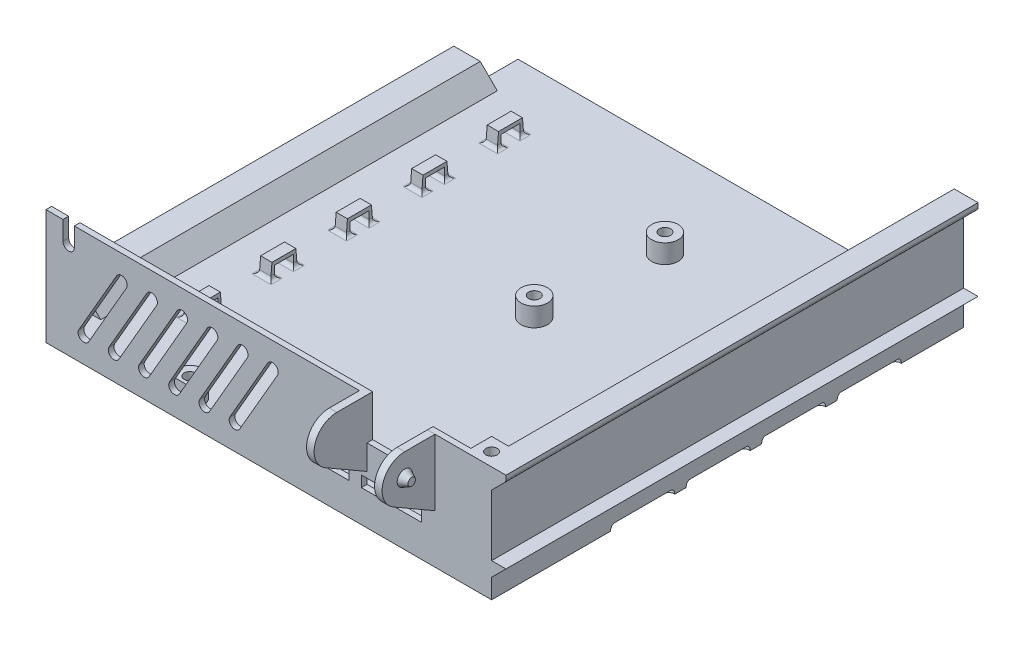
SolidWorks part; units mm, degrees
material "ABS"
ref_plane "Front Plane" through (0, 0, 0) normal (0, 0, 1) x (1, 0, 0)
ref_plane "Top Plane" through (0, 0, 0) normal (0, 1, 0) x (1, 0, 0)
ref_plane "Right Plane" through (0, 0, 0) normal (1, 0, 0) x (0, 0, -1)
ref_axis "Axis1" through (0, 0, 22) along (0, 0, -1)
sketch "Sketch1" plane through (0, 0, 0) normal (0, 1, 0) x (1, 0, 0)
  line L0 (-125, 0) -> (0, 0) construction
  line L1 (125, 0) -> (125, 125) construction
  line L2 (125, 125) -> (-125, 125) construction
  line L3 (-125, 125) -> (-125, 0) construction
  line L4 (41.25, 3.85) -> (41.25, 1.6) construction
  line L5 (39, 101.6) -> (109, 101.6)
  line L6 (39, 101.6) -> (39, 1.6)
  line L7 (39, 1.6) -> (109, 1.6)
  line L8 (109, 101.6) -> (109, 1.6)
  line L9 (39, 101.6) -> (109, 1.6) construction
  line L10 (39, 1.6) -> (109, 101.6) construction
  line L11 (41.25, 3.85) -> (39, 3.85) construction
  line L12 (-114.29, 77.51) -> (-116.54, 77.51) construction
  line L13 (78.2, 11.6) -> (87.2, 11.6)
  line L14 (78.2, 11.6) -> (78.2, 1.6)
  line L15 (78.2, 1.6) -> (87.2, 1.6)
  line L16 (87.2, 11.6) -> (87.2, 1.6)
  line L17 (78.2, 11.6) -> (87.2, 1.6) construction
  line L18 (78.2, 1.6) -> (87.2, 11.6) construction
  line L19 (90.5, 16.6) -> (106.5, 16.6)
  line L20 (90.5, 16.6) -> (90.5, 1.6)
  line L21 (90.5, 1.6) -> (106.5, 1.6)
  line L22 (106.5, 16.6) -> (106.5, 1.6)
  line L23 (90.5, 16.6) -> (106.5, 1.6) construction
  line L24 (90.5, 1.6) -> (106.5, 16.6) construction
  line L25 (-116.54, 113.59) -> (-93.46, 113.59)
  line L26 (-116.54, 113.59) -> (-116.54, 71.41)
  line L27 (-116.54, 71.41) -> (-93.46, 71.41)
  line L28 (-93.46, 113.59) -> (-93.46, 71.41)
  line L29 (-116.54, 113.59) -> (-93.46, 71.41) construction
  line L30 (-116.54, 71.41) -> (-93.46, 113.59) construction
  line L31 (-114.29, 77.51) -> (-114.29, 71.41) construction
  line L32 (-95.71, 107.49) -> (-95.71, 113.59) construction
  line L33 (-95.71, 107.49) -> (-93.46, 107.49) construction
  line L34 (-64.5, 85.45) -> (-68, 85.45) construction
  line L35 (-65, 88.95) -> (-15, 88.95)
  line L36 (-68, 85.95) -> (-68, 6.95)
  line L37 (-65, 3.95) -> (-15, 3.95)
  line L38 (-12, 85.95) -> (-12, 6.95)
  line L39 (-68, 88.95) -> (-12, 3.95) construction
  line L40 (-68, 3.95) -> (-12, 88.95) construction
  line L41 (-64.5, 85.45) -> (-15.5, 85.45) construction
  line L42 (-64.5, 85.45) -> (-64.5, 27.45) construction
  line L43 (-64.5, 27.45) -> (-15.5, 27.45) construction
  line L44 (-15.5, 85.45) -> (-15.5, 27.45) construction
  line L45 (0, 0) -> (0, 125) construction
  line L46 (0, 0) -> (125, 0) construction
  line L47 (-64.5, 85.45) -> (-64.5, 88.95) construction
  line L48 (74, 0.1) -> (74, 125) construction
  line L49 (-65.69, 22.9) -> (-49.81, 22.9)
  line L50 (-65.69, 22.9) -> (-65.69, 1.5)
  line L51 (-65.69, 1.5) -> (-49.81, 1.5)
  line L52 (-49.81, 22.9) -> (-49.81, 1.5)
  line L53 (-65.69, 22.9) -> (-49.81, 1.5) construction
  line L54 (-65.69, 1.5) -> (-49.81, 22.9) construction
  line L55 (-45.65, 19.42) -> (-32.35, 19.42)
  line L56 (-45.65, 19.42) -> (-45.65, 1.5)
  line L57 (-45.65, 1.5) -> (-32.35, 1.5)
  line L58 (-32.35, 19.42) -> (-32.35, 1.5)
  line L59 (-45.65, 19.42) -> (-32.35, 1.5) construction
  line L60 (-45.65, 1.5) -> (-32.35, 19.42) construction
  line L61 (-27.65, 19.42) -> (-14.35, 19.42)
  line L62 (-27.65, 19.42) -> (-27.65, 1.5)
  line L63 (-27.65, 1.5) -> (-14.35, 1.5)
  line L64 (-14.35, 19.42) -> (-14.35, 1.5)
  line L65 (-27.65, 19.42) -> (-14.35, 1.5) construction
  line L66 (-27.65, 1.5) -> (-14.35, 19.42) construction
  line L67 (-40, 0) -> (-40, 125) construction
  line L68 (-114.29, 11.41) -> (-114.29, 17.51) construction
  line L69 (-116.54, 53.59) -> (-93.46, 53.59)
  line L70 (-116.54, 53.59) -> (-116.54, 11.41)
  line L71 (-116.54, 11.41) -> (-93.46, 11.41)
  line L72 (-93.46, 53.59) -> (-93.46, 11.41)
  line L73 (-116.54, 53.59) -> (-93.46, 11.41) construction
  line L74 (-116.54, 11.41) -> (-93.46, 53.59) construction
  line L75 (-114.29, 17.51) -> (-116.54, 17.51) construction
  line L76 (-95.71, 53.59) -> (-95.71, 47.49) construction
  line L77 (-95.71, 47.49) -> (-93.46, 47.49) construction
  line L78 (-105, 0) -> (-105, 32.5) construction
  line L79 (-105, 32.5) -> (-105, 92.5) construction
  line L80 (-105, 92.5) -> (-105, 125) construction
  line L81 (-64.5, 27.45) -> (-15.5, 85.45) construction
  line L82 (-15.5, 27.45) -> (-64.5, 85.45) construction
  circle A0 centre (106, 81.6) radius 1.75
  circle A1 centre (106, 19.6) radius 1.75
  circle A2 centre (71.1, 99.8) radius 1.75
  circle A3 centre (68.3, 68) radius 1.75
  circle A4 centre (41.25, 3.85) radius 1.75
  circle A5 centre (-95.71, 107.49) radius 1.4
  circle A6 centre (-114.29, 77.51) radius 1.4
  arc A7 (-15, 3.95) -> (-12, 6.95) centre (-15, 6.95) ccw
  arc A8 (-68, 6.95) -> (-65, 3.95) centre (-65, 6.95) ccw
  arc A9 (-15, 88.95) -> (-12, 85.95) centre (-15, 85.95) cw
  arc A10 (-65, 88.95) -> (-68, 85.95) centre (-65, 85.95) ccw
  circle A11 centre (-64.5, 85.45) radius 1.375
  circle A12 centre (-15.5, 85.45) radius 1.375
  circle A13 centre (-64.5, 27.45) radius 1.375
  circle A14 centre (-15.5, 27.45) radius 1.375
  circle A15 centre (-95.71, 47.49) radius 1.4
  circle A16 centre (-114.29, 17.51) radius 1.4
  circle A17 centre (41.25, 3.85) radius 2.84
  point P0 (74, 51.6)
  point P3 (-105, 92.5)
  point P4 (0, 0)
  point P24 (82.7, 6.6)
  point P30 (98.5, 9.1)
  point P47 (-40, 46.45)
  point P65 (-39, 10.46)
  point P69 (-57.75, 12.2)
  point P84 (-21, 10.46)
  point P89 (-105, 32.5)
  point P111 (-40, 56.45)
  dimension "D5" = 3.5
  dimension "D26" = 3
  dimension "D27" = 2.75
  dimension "D44" = 2.8
  dimension "D49" = 5.68
  dimension "D1" = 250
  dimension "D2" = 125
  dimension "D3" = 100
  dimension "D4" = 70
  dimension "D6" = 20
  dimension "D7" = 3
  dimension "D8" = 82
  dimension "D9" = 1.8
  dimension "D10" = 37.9
  dimension "D11" = 33.6
  dimension "D12" = 40.7
  dimension "D13" = 2.25
  dimension "D14" = 9
  dimension "D15" = 10
  dimension "D16" = 26.3
  dimension "D17" = 16
  dimension "D18" = 15
  dimension "D19" = 10.5
  dimension "D20" = 23.08
  dimension "D21" = 42.18
  dimension "D22" = 6.1
  dimension "D23" = 2.25
  dimension "D24" = 85
  dimension "D25" = 56
  dimension "D28" = 58
  dimension "D29" = 49
  dimension "D30" = 10.25
  dimension "D31" = 29
  dimension "D32" = 47
  dimension "D33" = 21.4
  dimension "D34" = 15.88
  dimension "D35" = 2.45
  dimension "D36" = 13.3
  dimension "D37" = 17.92
  dimension "D38" = 2.45
  dimension "D39" = 2.45
  dimension "D40" = 2.25
  dimension "D41" = 1.6
  dimension "D42" = 40
  dimension "D43" = 1.5
  dimension "D45" = 60
  dimension "D46" = 3.5
  dimension "D47" = 20
  dimension "D48" = 16
sketch "Sketch2" plane through (0, 0, 0) normal (0, 1, 0) x (1, 0, 0)
  line L0 (125, 125) -> (-125, 125) construction
  line L1 (125, 0) -> (7, 0)
  line L2 (125, 0) -> (125, 125)
  line L3 (125, 125) -> (7, 125)
  line L4 (7, 0) -> (7, 125)
  line L5 (125, 0) -> (7, 125) construction
  line L6 (125, 125) -> (7, 0) construction
  point P4 (66, 62.5)
  dimension "D1" = 7
extrude "Boss-Extrude1" add sketch "Sketch2" along normal blind 2.5
sketch "Sketch3" plane through (0, 2.5, 0) normal (0, 1, 0) x (1, 0, 0)
  circle A0 centre (106, 19.6) radius 1.5
  circle A1 centre (68.3, 68) radius 1.5
  circle A2 centre (106, 81.6) radius 1.5
  circle A3 centre (71.1, 99.8) radius 1.5
  circle A4 centre (41.25, 3.85) radius 1.5
  circle A5 centre (41.25, 3.85) radius 3.5
  circle A6 centre (106, 19.6) radius 3.5
  circle A7 centre (68.3, 68) radius 3.5
  circle A8 centre (106, 81.6) radius 3.5
  circle A9 centre (71.1, 99.8) radius 3.5
  dimension "D1" = 3
  dimension "D2" = 2
extrude "Boss-Extrude2" add sketch "Sketch3" along normal blind 5
sketch "Sketch5" plane through (0, 2.5, 0) normal (0, 1, 0) x (1, 0, 0)
  line L0 (125, 0) -> (125, 125) construction
  line L1 (7, 0) -> (125, 0)
  line L2 (7, 0) -> (7, 1.5)
  line L3 (7, 1.5) -> (125, 1.5)
  line L4 (125, 0) -> (125, 1.5)
  line L5 (7, 0) -> (125, 1.5) construction
  line L6 (7, 1.5) -> (125, 0) construction
  point P4 (66, 0.75)
  dimension "D1" = 1.5
extrude "Boss-Extrude3" add sketch "Sketch5" along normal blind 28
sketch "Sketch6" plane through (0, 0, 0) normal (0, 0, 1) x (1, 0, 0)
  line L0 (78.2, 0) -> (87.2, 0) construction
  line L1 (78.2, 0) -> (87.2, 0) construction
  line L2 (90.5, 0) -> (106.5, 0) construction
  line L3 (90.5, 0) -> (106.5, 0) construction
  line L4 (78.2, 0) -> (78.2, 2.5) construction
  line L5 (78.2, 2.5) -> (78.2, 7.5) construction
  line L6 (78.2, 7.5) -> (78.2, 8.5) construction
  line L7 (78.2, 8.5) -> (87.2, 8.5)
  line L8 (87.2, 8.5) -> (87.2, 13.6)
  line L9 (87.2, 13.6) -> (78.2, 13.6)
  line L10 (78.2, 13.6) -> (78.2, 8.5)
  line L11 (90.5, 8.5) -> (106.5, 8.5)
  line L12 (106.5, 8.5) -> (106.5, 11.4)
  line L13 (106.5, 11.4) -> (90.5, 11.4)
  line L14 (90.5, 11.4) -> (90.5, 8.5)
  dimension "D1" = 2.5
  dimension "D2" = 5
  dimension "D3" = 1
  dimension "D4" = 9
  dimension "D5" = 16
  dimension "D6" = 2.9
  dimension "D7" = 5.1
extrude "Cut-Extrude1" cut sketch "Sketch6" against normal up to surface (1.5 mm away) up to face at (53.625, 10.75, -1.5)
sketch "Sketch7" plane through (0, 0, 0) normal (0, 0, 1) x (1, 0, 0)
  line L0 (125, 0) -> (125, 5.2)
  line L1 (125, 30.5) -> (125, 0) construction
  line L2 (125, 5.2) -> (126.8, 7)
  line L3 (126.8, 7) -> (126.8, 0) construction
  line L4 (126.8, 0) -> (125, 0) construction
  line L5 (126.8, 7) -> (122.5, 7)
  line L6 (122.5, 7) -> (122.5, 0)
  line L7 (7, 0) -> (125, 0) construction
  line L8 (122.5, 0) -> (125, 0)
  line L9 (125, 7) -> (125, 25.2)
  line L10 (126.8, 7) -> (126.8, 27) construction
  line L11 (125, 25.2) -> (126.8, 27)
  line L12 (126.8, 0) -> (128.8, 0) construction
  line L13 (128.8, 0) -> (128.8, 29) construction
  line L14 (126.8, 7) -> (128.8, 9)
  line L15 (126.8, 27) -> (128.8, 29)
  line L16 (122.5, 7) -> (122.5, 30.5)
  line L17 (7, 30.5) -> (125, 30.5) construction
  line L18 (122.5, 30.5) -> (128.8, 30.5)
  line L19 (128.8, 30.5) -> (128.8, 29)
  line L20 (128.8, 9) -> (122.5, 9)
  line M19 (7, 0) -> (125, 0)
  line M20 (125, 0) -> (125, 30.5)
  line M21 (125, 30.5) -> (7, 30.5)
  dimension "D1" = 5.2
  dimension "D2" = 7
  dimension "D3" = 1.8
  dimension "D4" = 2.5
  dimension "D5" = 25.2
  dimension "D6" = 27
  dimension "D7" = 2
extrude "Boss-Extrude4" add sketch "Sketch7" against normal up to surface (125 mm away) contours L5 L6 M19 M20 | L2 L5 M20 | L14 L20 L5 M20 | L20 L16 L5 M20 | L20 L9 L16 M20 M21 | L19 L18 L11 L15 M20 region at (123.75, 3.5, 0) region at (125.6, 6.4, 0) region at (126.4595, 8.119, 0) region at (123.75, 8, 0) region at (123.75, 19.75, 0) region at (126.5461, 28.623, 0) up to face at (66, 1.25, -125)
fillet "Fillet1" radius 1 1 edges at (128.8, 29, -62.5)
sketch "Sketch9" plane through (0, 0, 0) normal (0, 0, 1) x (1, 0, 0)
  line L0 (7, 7) -> (11.5, 2.5)
  line L1 (7, 0) -> (0, 0)
  line L2 (7, 0) -> (7, 7)
  line L3 (7, 7) -> (0, 7)
  line L4 (0, 0) -> (0, 7)
  line L5 (7, 0) -> (0, 7) construction
  line L6 (7, 7) -> (0, 0) construction
  line L7 (11.5, 2.5) -> (7, 2.5)
  line L8 (7, 0) -> (125, 0) construction
  circle A0 centre (3.5, 3.5) radius 1.5
  point P4 (3.5, 3.5)
  line M15 (7, 30.5) -> (7, 0)
  dimension "D2" = 3
  dimension "D1" = 7
  dimension "D3" = 2.5
  dimension "D4" = 45
extrude "Boss-Extrude5" add sketch "Sketch9" against normal offset from surface (105 mm away) 10 from offset 10 contours L4 L1 L2 L3 A0 M15 | L7 L0 M15 region at (8.5, 4, 0) region at (6.901, 4.75, 0) up to face at (106.1648, 14.3743, -125) offset against normal yes
sketch "Sketch12" plane through (0, 30.5, 0) normal (0, 1, 0) x (1, 0, 0)
  line L1 (125, 0) -> (118, 0)
  line L2 (125, 0) -> (125, 7)
  line L3 (125, 7) -> (118, 7)
  line L4 (118, 0) -> (118, 7)
  line L5 (125, 0) -> (118, 7) construction
  line L6 (125, 7) -> (118, 0) construction
  circle A0 centre (121.5, 3.5) radius 1.5 construction
  point P4 (121.5, 3.5)
  dimension "D2" = 3
  dimension "D1" = 7
extrude "Boss-Extrude7" add sketch "Sketch12" against normal up to surface (28 mm away) up to face at (37.85, 2.5, -51.185)
sketch "Sketch13" plane through (0, 30.5, 0) normal (0, 1, 0) x (1, 0, 0)
  circle A0 centre (121.5, 3.5) radius 1.5 construction
  circle A1 centre (121.5, 3.5) radius 1.5
extrude "Cut-Extrude3" cut sketch "Sketch13" against normal blind 10
sketch "Sketch15" plane through (0, 0, 0) normal (-1, 0, 0) x (0, 0, 1)
  line L0 (-125, 2.5) -> (-1.5, 2.5) construction
  line L1 (-107.5, 2.5) -> (-108.5, 2.5)
  line L2 (-107.5, 2.5) -> (-102.5, 2.5) construction
  line L3 (-107.5, 2.5) -> (-107.5, 5.5)
  line L4 (-107.5, 5.5) -> (-102.5, 5.5)
  line L5 (-102.5, 2.5) -> (-102.5, 5.5)
  line L6 (-107.5, 2.5) -> (-102.5, 5.5) construction
  line L7 (-107.5, 5.5) -> (-102.5, 2.5) construction
  line L8 (-108.5, 2.5) -> (-108.1701, 6.5)
  line L9 (-108.1701, 6.5) -> (-101.8299, 6.5)
  line L10 (-101.8299, 6.5) -> (-101.5, 2.5)
  line L11 (-101.5, 2.5) -> (-102.5, 2.5)
  line L12 (-115, 7) -> (-115, 0) construction
  point P8 (-105, 4)
  dimension "D1" = 3
  dimension "D2" = 5
  dimension "D3" = 1
  dimension "D4" = 1
  dimension "D5" = 0.75
  dimension "D6" = 10
extrude "Boss-Extrude8" add sketch "Sketch15" along normal blind 3 from offset 25 offset against normal yes
pattern_linear "LPattern1" count 5 spacing 20 along (0, 0, 1) of "Boss-Extrude8"
fillet "Fillet2" radius 1 40 edges at (25, 2.5, -62) (23.5, 2.5, -62.5) (23.5, 2.5, -61.5) (22, 2.5, -62) (25, 2.5, -68) (22, 2.5, -68) (23.5, 2.5, -67.5) (23.5, 2.5, -68.5) (25, 2.5, -82) (23.5, 2.5, -82.5) (23.5, 2.5, -81.5) (22, 2.5, -82) (25, 2.5, -88) (23.5, 2.5, -88.5) (23.5, 2.5, -87.5) (22, 2.5, -88) (25, 2.5, -102) (23.5, 2.5, -102.5) (23.5, 2.5, -101.5) (22, 2.5, -102) (25, 2.5, -108) (23.5, 2.5, -108.5) (23.5, 2.5, -107.5) (22, 2.5, -108) (25, 2.5, -22) (23.5, 2.5, -22.5) (23.5, 2.5, -21.5) (22, 2.5, -22) (25, 2.5, -28) (23.5, 2.5, -28.5) (23.5, 2.5, -27.5) (22, 2.5, -28) (25, 2.5, -42) (23.5, 2.5, -42.5) (23.5, 2.5, -41.5) (22, 2.5, -42) (25, 2.5, -48) (23.5, 2.5, -48.5) (23.5, 2.5, -47.5) (22, 2.5, -48)
sketch "Sketch16" plane through (0, 0, 0) normal (0, 0, 1) x (1, 0, 0)
  line L0 (27, 23.9103) -> (17, 6.5897) construction
  line L1 (28.299, 23.1603) -> (18.299, 5.8397)
  line L2 (25.701, 24.6603) -> (15.701, 7.3397)
  line L3 (17, 6.5897) -> (27, 6.5897) construction
  line L4 (27, 6.5897) -> (27, 23.9103) construction
  line L5 (7, 15.25) -> (125, 15.25) construction
  line L6 (7, 30.5) -> (7, 0) construction
  line L7 (125, 25.2) -> (125, 9) construction
  arc A0 (28.299, 23.1603) -> (25.701, 24.6603) centre (27, 23.9103) ccw
  arc A1 (15.701, 7.3397) -> (18.299, 5.8397) centre (17, 6.5897) ccw
  point P2 (22, 15.25)
  dimension "D3" = 1.5
  dimension "D1" = 60
  dimension "D2" = 20
  dimension "D4" = 15
extrude "Cut-Extrude4" cut sketch "Sketch16" against normal up to surface (1.5 mm away) up to face at (82.7, 11.05, -1.5)
pattern_linear "LPattern2" count 6 spacing 8 along (1, 0, 0) of "Cut-Extrude4"
ref_plane "Plane2" through (60, -60, 0) normal (-0.7071, 0.7071, 0) x (0, 0, 1)
sketch "Sketch18" plane through (60, -60, 0) normal (-0.7071, 0.7071, 0) x (0, 0, 1)
  line L0 (-107.5, 88.3883) -> (-92.5, 88.3883) construction
  line L1 (-125, 88.3883) -> (-7, 88.3883) construction
  line L2 (-107.5, 89.3883) -> (-92.5, 89.3883)
  line L3 (-107.5, 87.3883) -> (-92.5, 87.3883)
  arc A0 (-107.5, 89.3883) -> (-107.5, 87.3883) centre (-107.5, 88.3883) ccw
  arc A1 (-92.5, 87.3883) -> (-92.5, 89.3883) centre (-92.5, 88.3883) ccw
  point P4 (-100, 88.3883)
  dimension "D1" = 15
  dimension "D2" = 1
  dimension "D3" = 25
extrude "Cut-Extrude5" cut sketch "Sketch18" against normal through all both and the other way through all
pattern_linear "LPattern3" count 4 spacing 20 along (0, 0, 1) of "Cut-Extrude5"
ref_plane "Plane3" through (100, 0, 0) normal (1, 0, 0) x (0, 0, -1)
ref_plane "Plane4" through (110, 0, 0) normal (1, 0, 0) x (0, 0, -1)
sketch "Sketch20" plane through (110, 0, 0) normal (1, 0, 0) x (0, 0, -1)
  line L0 (0, 25.2) -> (0, 9) construction
  line L1 (125, 30.5) -> (0, 30.5) construction
  line L2 (-8, 30.5) -> (0, 30.5)
  line L3 (-11, 19.3038) -> (0, 12.953)
  line L4 (0, 30.5) -> (0, 12.953)
  arc A0 (-8, 30.5) -> (-11, 19.3038) centre (-8, 24.5) ccw
  dimension "D1" = 12
  dimension "D3" = 60
  dimension "D2" = 8
extrude "Boss-Extrude9" add sketch "Sketch20" against normal blind 2 separate body
ref_plane "Plane5" through (0, 0, 8) normal (0, 0, 1) x (1, 0, 0)
sketch "Sketch24" plane through (0, 0, 8) normal (0, 0, 1) x (1, 0, 0)
  line L0 (110, 24.5) -> (111.84, 24.5)
  line L1 (111.84, 24.5) -> (111.84, 25.5)
  line L2 (111.84, 25.5) -> (110, 26.5)
  line L3 (110, 26.5) -> (110, 24.5)
  dimension "D1" = 1.84
  dimension "D2" = 2
  dimension "D3" = 1
revolve "Revolve1" add sketch "Sketch24" angle 360 about L0
mirror "Mirror2" about plane through (100, 0, 0) normal (1, 0, 0) of "Revolve1", "Boss-Extrude9"
sketch "Sketch25" plane through (0, 0, 0) normal (0, 0, 1) x (1, 0, 0)
  line L0 (108, 30.5) -> (108, 19.3038) construction
  line L1 (92, 30.5) -> (108, 30.5)
  line L2 (92, 30.5) -> (92, 19.5)
  line L3 (92, 19.5) -> (108, 19.5)
  line L4 (108, 30.5) -> (108, 19.5)
  line L5 (92, 30.5) -> (108, 19.5) construction
  line L6 (92, 19.5) -> (108, 30.5) construction
  point P4 (100, 25)
  dimension "D1" = 11
extrude "Cut-Extrude6" cut sketch "Sketch25" against normal up to surface (1.5 mm away) up to face at (38, 15.25, -1.5)
sketch "Sketch26" plane through (0, 0, 0) normal (0, 0, 1) x (1, 0, 0)
  line L0 (13, 30.5) -> (13, 25.5) construction
  line L1 (7, 30.5) -> (90, 30.5) construction
  line L2 (14.5, 30.5) -> (14.5, 25.5)
  line L3 (11.5, 30.5) -> (11.5, 25.5)
  line L4 (7, 30.5) -> (7, 0) construction
  line L5 (11.5, 30.5) -> (14.5, 30.5)
  arc A0 (14.5, 30.5) -> (11.5, 30.5) centre (13, 30.5) ccw
  arc A1 (11.5, 25.5) -> (14.5, 25.5) centre (13, 25.5) ccw
  point P4 (13, 28)
  line M41 (90, 30.5) -> (7, 30.5)
  dimension "D1" = 5
  dimension "D2" = 1.5
  dimension "D3" = 6
extrude "Cut-Extrude7" cut sketch "Sketch26" against normal up to surface (1.5 mm away) contours L3 A1 L2 L5 M41 region at (13, 27.4019, 0) up to face at (62.5501, 15.6325, -1.5)
equation "\"D16@Sketch1\"=22.8+3.5"
equation "\"D19@Sketch1\"=7+3.5"
equation "\"D1@Boss-Extrude3\"=33-2.5-2.5"
